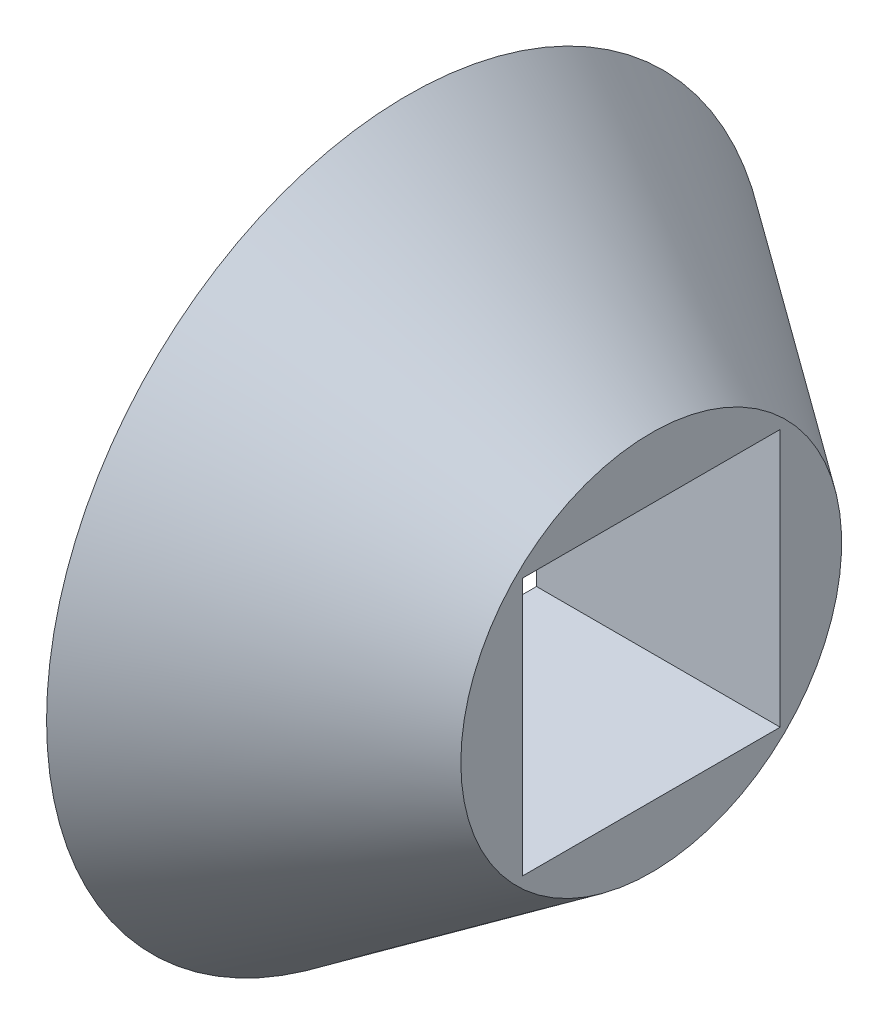
SolidWorks part; units mm, degrees
material "Custom Plastic"
ref_plane "Front Plane" through (0, 0, 0) normal (0, 0, 1) x (1, 0, 0)
ref_plane "Top Plane" through (0, 0, 0) normal (0, 1, 0) x (1, 0, 0)
ref_plane "Right Plane" through (0, 0, 0) normal (1, 0, 0) x (0, 0, -1)
sketch "Sketch1" plane through (0, 0, 0) normal (1, 0, 0) x (0, 0, -1)
  line L1 (1.5875, -1.5875) -> (-1.5875, -1.5875)
  line L2 (1.5875, -1.5875) -> (1.5875, 1.5875)
  line L3 (1.5875, 1.5875) -> (-1.5875, 1.5875)
  line L4 (-1.5875, -1.5875) -> (-1.5875, 1.5875)
  line L5 (1.5875, -1.5875) -> (-1.5875, 1.5875) construction
  line L6 (1.5875, 1.5875) -> (-1.5875, -1.5875) construction
  circle A0 centre (0, 0) radius 4.445
  dimension "D2" = 8.89
  dimension "D1" = 3.175
extrude "Boss-Extrude1" add sketch "Sketch1" along normal blind 3
sketch "Sketch2" plane through (0, 0, 0) normal (0, 0, 1) x (1, 0, 0)
  line L0 (0, 4.445) -> (3, 4.445)
  line L1 (0, 4.445) -> (0, -4.445) construction
  line L2 (3, 4.445) -> (0, 4.445) construction
  line L3 (3, -4.445) -> (3, 4.445) construction
  line L4 (3, 4.445) -> (3, 2.3444)
  line L5 (3, 2.3444) -> (0, 4.445)
  line L6 (0, 0) -> (3, 0) construction
  dimension "D1" = 35
revolve "Cut-Revolve1" cut sketch "Sketch2" angle 360 about L6
